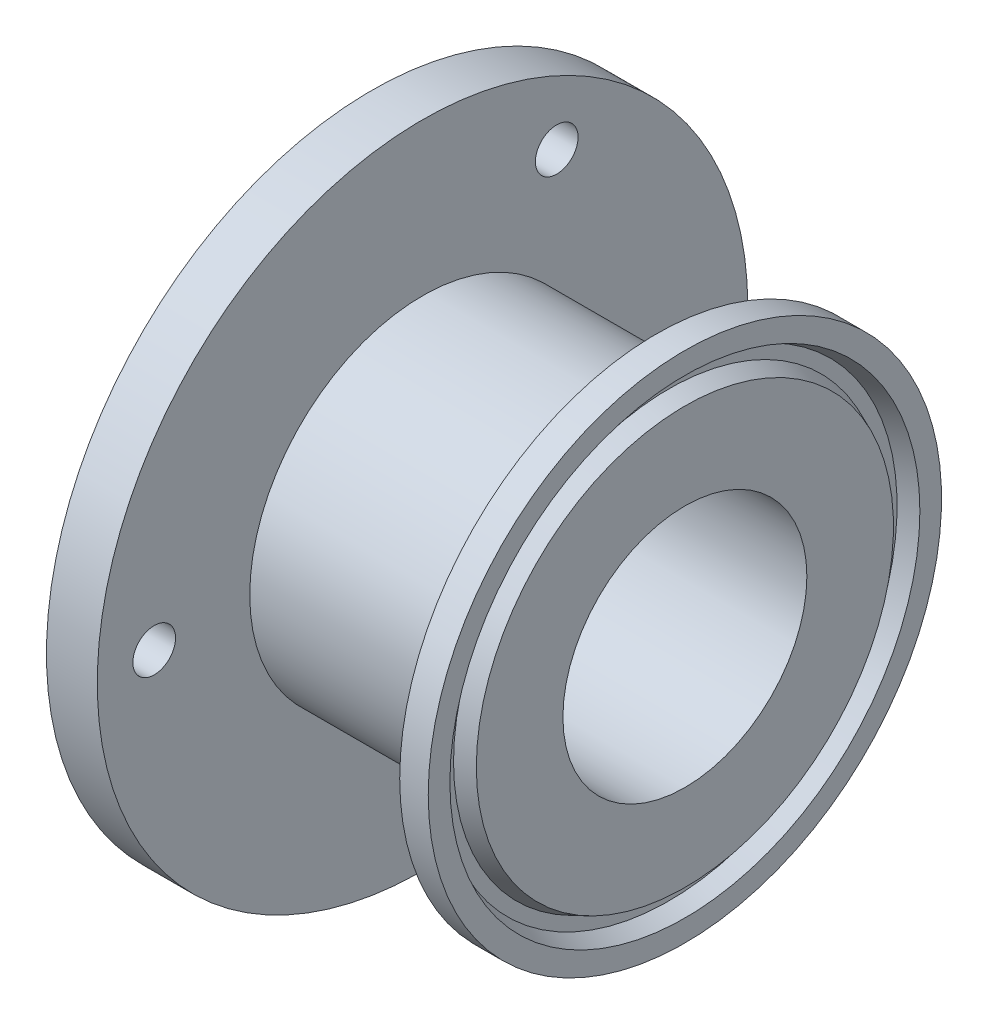
SolidWorks part; units mm, degrees
material "6061 Alloy"
ref_plane "Front Plane" through (0, 0, 0) normal (0, 0, 1) x (1, 0, 0)
ref_plane "Top Plane" through (0, 0, 0) normal (0, 1, 0) x (1, 0, 0)
ref_plane "Right Plane" through (0, 0, 0) normal (1, 0, 0) x (0, 0, -1)
sketch "Sketch1" plane through (0, 0, 0) normal (0, 0, 1) x (1, 0, 0)
  line L0 (-15.4047, 12) -> (-15.4047, 34)
  line L1 (-15.4047, 34) -> (-10.4047, 34)
  line L2 (-10.4047, 34) -> (-10.4047, 17)
  line L3 (-10.4047, 17) -> (8.7949, 17)
  line L4 (9.869, 17.7521) -> (12.598, 25.25)
  line L5 (12.598, 25.25) -> (15.4047, 25.25)
  line L6 (15.4047, 25.25) -> (15.4047, 23.1186)
  line L7 (15.4047, 12) -> (-15.4047, 12)
  line L8 (0, 0) -> (52.6945, 0) construction
  line L9 (0, 12) -> (0, 0) construction
  line L10 (15.4047, 23.1186) -> (13.8299, 22.4501)
  line L11 (13.8299, 22.4501) -> (13.8299, 21.1871)
  line L12 (13.8299, 21.1871) -> (15.4047, 20.5186)
  line L13 (13.8299, 21.8186) -> (15.4047, 21.8186) construction
  line L14 (15.4047, 20.5186) -> (15.4047, 12)
  arc A0 (8.7949, 17) -> (9.869, 17.7521) centre (8.7949, 18.143) ccw
  circle A1 centre (15.4047, 21.8186) radius 1.15 construction
  point P16 (9.5953, 17)
  dimension "D9" = 1.143
  dimension "D14" = 2.3
  dimension "D1" = 20
  dimension "D2" = 25.25
  dimension "D3" = 2.8067
  dimension "D4" = 5
  dimension "D5" = 68
  dimension "D6" = 5
  dimension "D7" = 20
  dimension "D8" = 22
  dimension "D10" = 46
  dimension "D11" = 21.8186
  dimension "D12" = 1.5748
  dimension "D13" = 2.6
revolve "Revolve1" add sketch "Sketch1" angle 360 about L8
hole_wizard "M5 Tapped Hole1" positions "Sketch2" profile "Sketch4" tap size "M5" standard "ISO"
sketch "Sketch2" plane through (-15.4047, 0, 0) normal (-1, 0, 0) x (0, 0, 1)
  point P0 (-13.2, -22.8631)
  point P3 (-13.2, 22.8631)
  point P6 (26.4, 0)
sketch "Sketch4" plane through (-15.4047, -22.8631, -13.2) normal (0, 1, 0) x (0, 0, 1)
  line L0 (0, 0) -> (0, 13.6618)
  line L1 (0, 13.6618) -> (2.1, 12.4)
  line L2 (2.1, 12.4) -> (2.1, 0)
  line L5 (2.1, 0) -> (0, 0)
  line L10 (0, 13.6618) -> (-2.1, 12.4) construction
  line L11 (0, -6.35) -> (0, 107.95) construction
  dimension "Tap Drill Dia." = 4.2
  dimension "Tap Drill Depth" = 12.4
  dimension "Drill Angle" = 118
cosmetic thread "Hole Thread1" parameters "D1"=10, "D2"=5
cosmetic thread "Hole Thread2" parameters "D1"=10, "D2"=5
cosmetic thread "Hole Thread3" parameters "D1"=10, "D2"=5
fillet "Fillet1" [suppressed] radius 1.1938
fillet "Fillet2" [suppressed] radius 0.7874
sketch "Sketch5" plane through (-10.4047, 0, 0) normal (1, 0, 0) x (0, 0, -1)
  circle A0 centre (0, 0) radius 32
  dimension "D1" = 64
extrude "Cut-Extrude-Thin1" cut sketch "Sketch5" against normal through all thin thin type one direction wall 10
ref_axis "Axis1" through (-12.5452, 0, 0) along (1, 0, 0)
